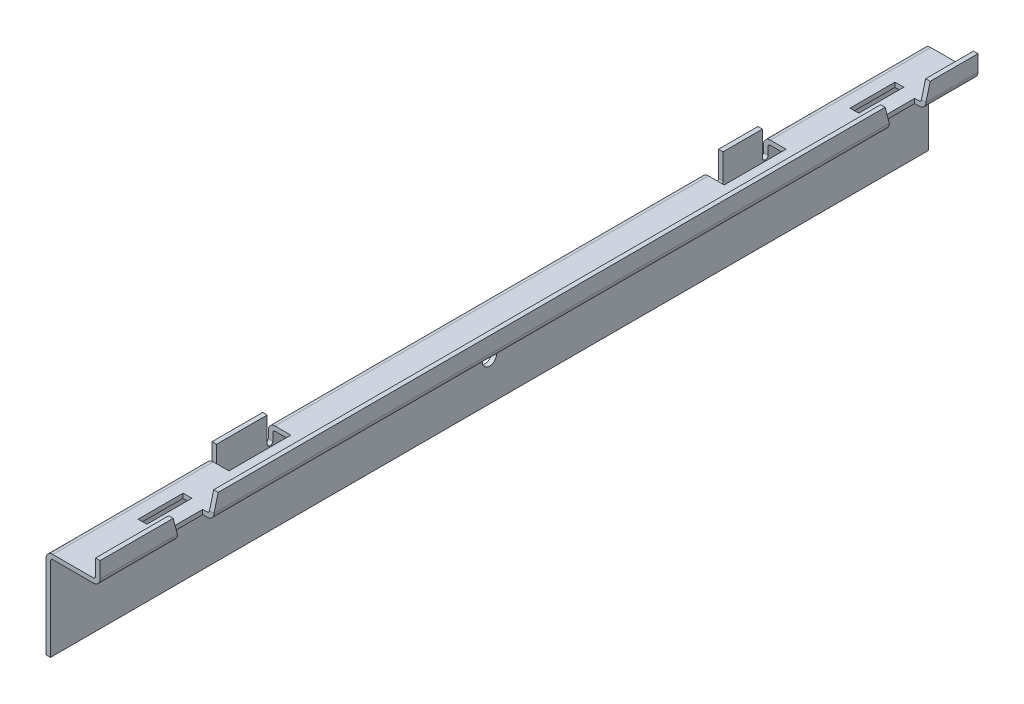
SolidWorks part; units mm, degrees
ref_plane "Front Plane" through (0, 0, 0) normal (0, 0, 1) x (1, 0, 0)
ref_plane "Top Plane" through (0, 0, 0) normal (0, 1, 0) x (1, 0, 0)
ref_plane "Right Plane" through (0, 0, 0) normal (1, 0, 0) x (0, 0, -1)
sketch "Sketch1" plane through (0, 0, 0) normal (0, 0, 1) x (1, 0, 0)
  line L0 (-3.5123, 50.7755) -> (-3.5123, -0.1833)
  line L1 (-3.5123, -0.1833) -> (-0.9723, -0.1833)
  line L2 (-0.9723, -0.1833) -> (-0.9723, 48.2355)
  line L3 (24.4277, 50.7755) -> (24.4277, 61.0942)
  line L4 (-3.5123, 50.7755) -> (24.4277, 50.7755)
  line L5 (26.9677, 48.2355) -> (-0.9723, 48.2355)
  line L6 (26.9677, 61.0942) -> (26.9677, 48.2355)
  line L7 (24.4277, 61.0942) -> (26.9677, 61.0942)
  dimension "D1" = 30.48
  dimension "D2" = 2.54
  dimension "D3" = 2.54
  dimension "D4" = 10.3187
  dimension "D5" = 2.54
  dimension "D6" = 48.4187
extrude "Extrude1" add sketch "Sketch1" along normal mid plane 495.3
fillet "Fillet2" radius 1.27 2 edges at (-0.9723, 48.2355, 0) (24.4277, 50.7755, 0)
fillet "Fillet3" radius 3.81 2 edges at (26.9677, 48.2355, 0) (-3.5123, 50.7755, 0)
sketch "Sketch2" plane through (-3.5123, 0, 0) normal (-1, 0, 0) x (0, 0, 1)
  line L0 (0, 0) -> (0, 61.0942) construction
  line L1 (247.65, 61.0942) -> (-247.65, 61.0942) construction
  line L2 (0, 50.7755) -> (-157.1625, 50.7755) construction
  line L4 (-157.1625, 50.7755) -> (-157.1625, 41.2505)
  line L5 (-157.1625, 41.2505) -> (-122.2375, 41.2505)
  line L6 (-122.2375, 41.2505) -> (-122.2375, 50.7755)
  line L7 (-122.2375, 50.7755) -> (-157.1625, 50.7755)
  line L8 (0, 50.7755) -> (157.1625, 50.7755) construction
  line L9 (157.1625, 50.7755) -> (157.1625, 41.2505)
  line L10 (157.1625, 41.2505) -> (122.2375, 41.2505)
  line L11 (122.2375, 41.2505) -> (122.2375, 50.7755)
  line L12 (122.2375, 50.7755) -> (157.1625, 50.7755)
  line L13 (247.65, 50.7755) -> (-247.65, 50.7755) construction
  dimension "D1" = 34.925
  dimension "D2" = 9.525
  dimension "D3" = 34.925
  dimension "D4" = 9.525
  dimension "D5" = 157.1625
  dimension "D6" = 157.1625
extrude "Cut-Extrude1" cut sketch "Sketch2" against normal blind 12.7
sketch "Sketch3" plane through (0, 41.2505, 0) normal (0, 1, 0) x (1, 0, 0)
  line L0 (9.1877, 157.1625) -> (0.2977, 157.1625) construction
  line L2 (-0.9723, 153.9875) -> (-3.5123, 153.9875)
  line L3 (-3.5123, 153.9875) -> (-3.5123, 131.7625)
  line L4 (-3.5123, 157.1625) -> (-3.5123, 122.2375) construction
  line L5 (-3.5123, 131.7625) -> (-0.9723, 131.7625)
  line L6 (-0.9723, 131.7625) -> (-0.9723, 153.9875)
  line L7 (9.1877, -157.1625) -> (0.2977, -157.1625) construction
  line L9 (-0.9723, -153.9875) -> (-3.5123, -153.9875)
  line L10 (-3.5123, -122.2375) -> (-3.5123, -157.1625) construction
  line L11 (-3.5123, -153.9875) -> (-3.5123, -125.4125)
  line L12 (-3.5123, -125.4125) -> (-0.9723, -125.4125)
  line L13 (-0.9723, -125.4125) -> (-0.9723, -153.9875)
  line L14 (9.1877, -122.2375) -> (0.2977, -122.2375) construction
  line L15 (-0.9723, -122.2375) -> (-0.9723, -157.1625) construction
  line L16 (-0.9723, 157.1625) -> (-0.9723, 122.2375) construction
  dimension "D1" = 3.175
  dimension "D2" = 3.175
  dimension "D3" = 3.175
  dimension "D4" = 22.225
extrude "Extrude2" add sketch "Sketch3" along normal blind 15.875
fillet "Fillet1" radius 1.5875 7 edges at (-2.2423, 41.2505, -153.9875) (-2.2423, 41.2505, -131.7625) (-2.2423, 41.2505, -157.1625) (-2.2423, 41.2505, 153.9875) (-2.2423, 41.2505, 122.2375) (-2.2423, 41.2505, 157.1625) (-2.2423, 41.2505, 125.4125)
sketch "Sketch4" plane through (0, 50.7755, 0) normal (0, 1, 0) x (1, 0, 0)
  line L0 (23.1577, 247.65) -> (0.2977, 247.65) construction
  line L3 (7.1557, 195.2625) -> (7.1557, 220.6625)
  line L4 (7.1557, 220.6625) -> (12.1087, 220.6625)
  line L5 (12.1087, 220.6625) -> (12.1087, 195.2625)
  line L6 (12.1087, 195.2625) -> (7.1557, 195.2625)
  line L9 (23.1577, -247.65) -> (0.2977, -247.65) construction
  line L10 (7.1557, -180.975) -> (7.1557, -206.375)
  line L11 (7.1557, -206.375) -> (12.1087, -206.375)
  line L12 (12.1087, -206.375) -> (12.1087, -180.975)
  line L13 (12.1087, -180.975) -> (7.1557, -180.975)
  line L16 (-3.5123, -247.65) -> (-3.5123, -157.1625) construction
  line L17 (-3.5123, 157.1625) -> (-3.5123, 247.65) construction
  dimension "D1" = 41.275
  dimension "D2" = 26.9875
  dimension "D3" = 4.953
  dimension "D4" = 4.953
  dimension "D5" = 10.668
  dimension "D6" = 10.668
  dimension "D7" = 25.4
  dimension "D8" = 25.4
extrude "Cut-Extrude2" cut sketch "Sketch4" against normal up to surface (2.54 mm away) up to face at (7.0711, 48.2355, 0)
sketch "Sketch5" plane through (26.9677, 0, 0) normal (1, 0, 0) x (0, 0, -1)
  line L0 (195.2625, 52.0455) -> (195.2625, 61.0942) construction
  line L2 (220.6625, 52.0455) -> (220.6625, 61.0942) construction
  line L3 (195.2625, 61.0942) -> (220.6625, 61.0942)
  line L4 (195.2625, 52.0455) -> (197.6437, 52.0455) construction
  line L6 (220.6625, 52.0455) -> (218.2812, 52.0455) construction
  line L7 (197.6437, 52.0455) -> (197.6437, 48.2355)
  line L9 (197.6437, 48.2355) -> (218.2812, 48.2355)
  line L10 (218.2812, 48.2355) -> (218.2812, 52.0455)
  line L11 (220.6625, 61.0942) -> (218.2812, 52.0455)
  line L12 (195.2625, 61.0942) -> (197.6437, 52.0455)
  line L13 (-206.375, 52.0455) -> (-206.375, 61.0942) construction
  line L14 (-180.975, 52.0455) -> (-180.975, 61.0942) construction
  line L15 (-180.975, 61.0942) -> (-206.375, 61.0942)
  line L16 (-206.375, 52.0455) -> (-203.9938, 52.0455) construction
  line L17 (-180.975, 52.0455) -> (-183.3562, 52.0455) construction
  line L18 (-183.3562, 52.0455) -> (-183.3562, 48.2355)
  line L19 (-183.3562, 48.2355) -> (-203.9938, 48.2355)
  line L20 (-203.9938, 48.2355) -> (-203.9938, 52.0455)
  line L21 (-206.375, 61.0942) -> (-203.9938, 52.0455)
  line L22 (-180.975, 61.0942) -> (-183.3562, 52.0455)
  line L23 (-247.65, 52.0455) -> (-247.65, 61.0942) construction
  line L24 (-247.65, 52.0455) -> (247.65, 52.0455) construction
  line L25 (247.65, 52.0455) -> (247.65, 61.0942) construction
  dimension "D1" = 20.6375
  dimension "D2" = 25.4
  dimension "D3" = 41.275
  dimension "D4" = 25.4
  dimension "D5" = 20.6375
  dimension "D6" = 26.9875
extrude "Cut-Extrude3" cut sketch "Sketch5" against normal blind 6.35
sketch "Sketch6" plane through (-3.5123, 0, 0) normal (-1, 0, 0) x (0, 0, 1)
  line L0 (0, 0) -> (0, 22.225) construction
  circle A0 centre (0, 22.225) radius 3.9688
  dimension "D1" = 22.225
extrude "Cut-Extrude4" cut sketch "Sketch6" against normal up to surface (2.54 mm away) up to face at (-0.9723, 42.2394, -0.8074)
